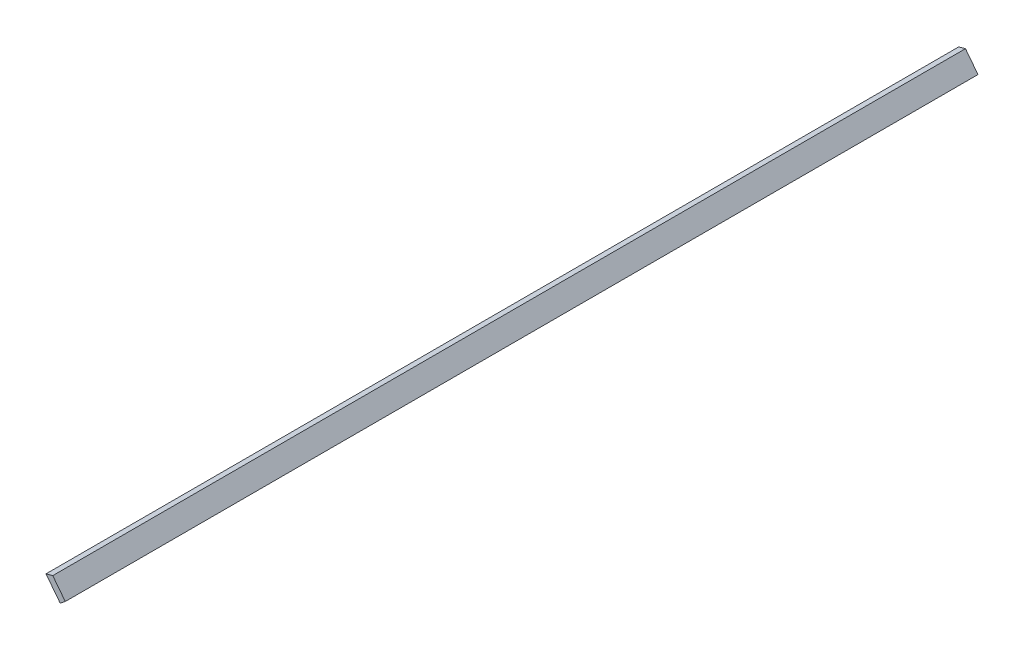
SolidWorks part; units mm, degrees
ref_plane "Front Plane" through (0, 0, 0) normal (0, 0, 1) x (1, 0, 0)
ref_plane "Top Plane" through (0, 0, 0) normal (0, 1, 0) x (1, 0, 0)
ref_plane "Right Plane" through (0, 0, 0) normal (1, 0, 0) x (0, 0, -1)
sketch "Sketch1" plane through (0, 0, 0) normal (0, 0, 1) x (1, 0, 0)
  line L0 (0, 0) -> (5.0245, 3.8829)
  line L1 (5.0245, 3.8829) -> (-7.2453, 19.7604)
  line L2 (-7.2453, 19.7604) -> (-13.8782, 17.9587)
  line L3 (-13.8782, 17.9587) -> (0, 0)
  dimension "D1" = 6.35
  dimension "D2" = 67.5
  dimension "D3" = 90
  dimension "D4" = 20.066
extrude "Boss-Extrude1" add sketch "Sketch1" along normal blind 895.35
